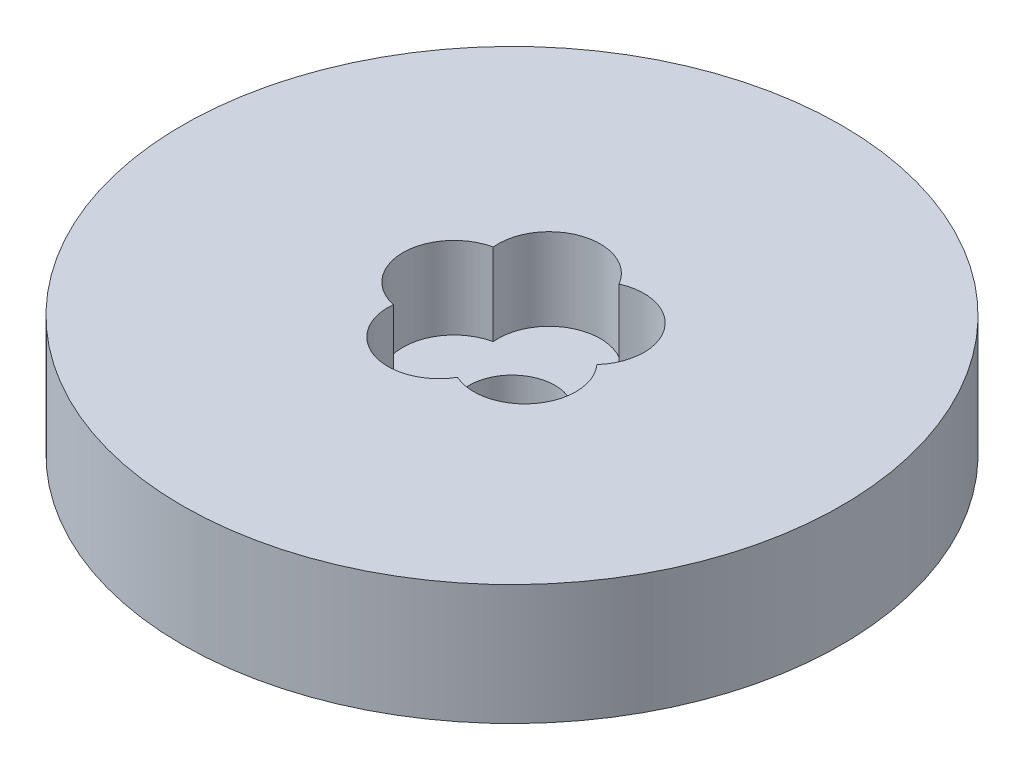
SolidWorks part; units mm, degrees
ref_plane "Front Plane" through (0, 0, 0) normal (0, 0, 1) x (1, 0, 0)
ref_plane "Top Plane" through (0, 0, 0) normal (0, 1, 0) x (1, 0, 0)
ref_plane "Right Plane" through (0, 0, 0) normal (1, 0, 0) x (0, 0, -1)
sketch "Sketch1" plane through (0, 0, 0) normal (0, 1, 0) x (1, 0, 0)
  circle A0 centre (0, 0) radius 57.5
  dimension "FLANGE_OD" = 115
extrude "Boss-Extrude1" add sketch "Sketch1" along normal blind 21
sketch "Sketch2" plane through (0, 0, 0) normal (0, 1, 0) x (1, 0, 0)
  circle A0 centre (0, 0) radius 7.5
  dimension "BORE_D" = 15
extrude "Cut-Extrude1" cut sketch "Sketch2" along normal through all
sketch "Sketch3" plane through (0, 21, 0) normal (0, 1, 0) x (1, 0, 0)
  circle A0 centre (0, 0) radius 10.109 construction
  circle A1 centre (-10.109, 0) radius 8.914
  dimension "BOLT_D" = 17.8281
  dimension "BOLT_PCD" = 20.218
extrude "Cut-Extrude2" cut sketch "Sketch3" against normal blind 14.3
pattern_circular "CirPattern1" count 5 over 360 about axis through (0, 0, 0) along (0, 1, 0) of "Cut-Extrude2"
